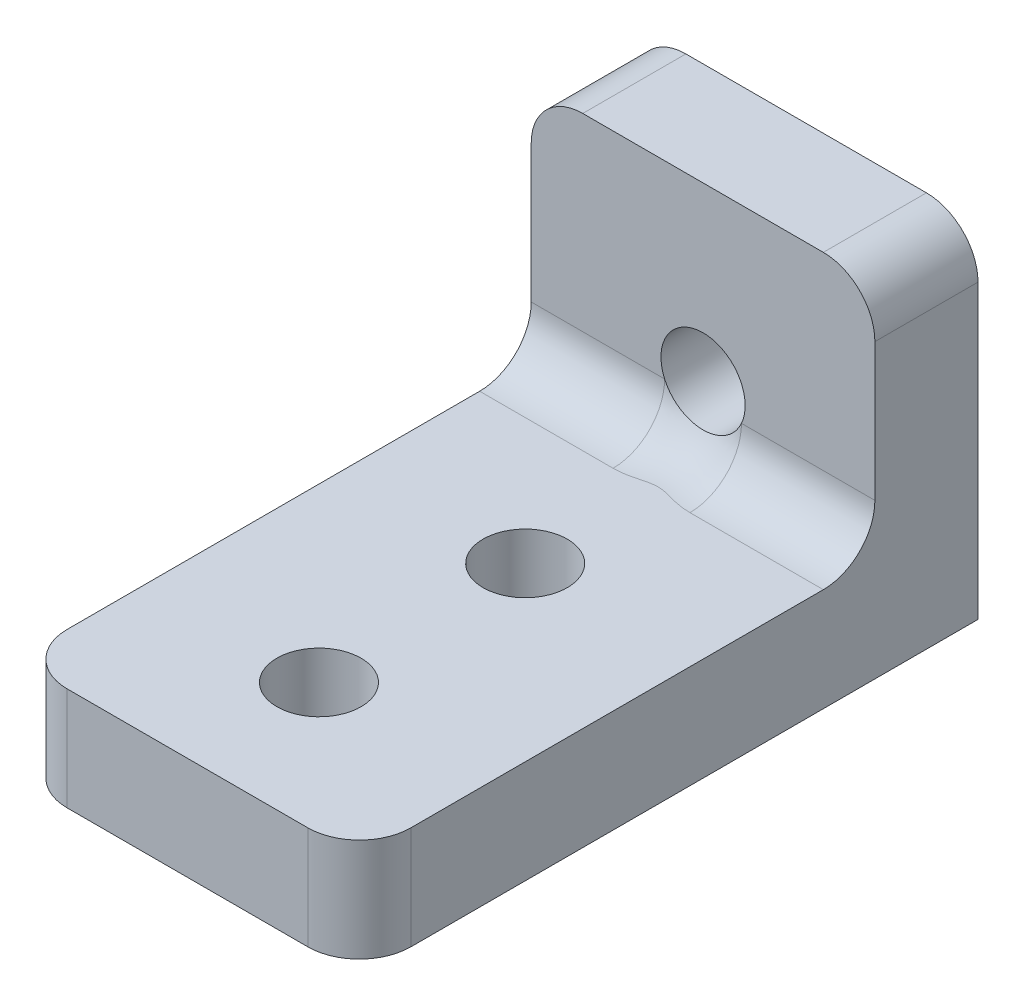
SolidWorks part; units mm, degrees
ref_plane "Front Plane" through (0, 0, 0) normal (0, 0, 1) x (1, 0, 0)
ref_plane "Top Plane" through (0, 0, 0) normal (0, 1, 0) x (1, 0, 0)
ref_plane "Right Plane" through (0, 0, 0) normal (1, 0, 0) x (0, 0, -1)
sketch "Sketch1" plane through (0, 0, 0) normal (0, 0, 1) x (1, 0, 0)
  line L1 (0, 0) -> (20, 0)
  line L2 (0, 0) -> (0, -20)
  line L3 (0, -20) -> (20, -20)
  line L4 (20, 0) -> (20, -20)
  dimension "D1" = 20
  dimension "D2" = 20
extrude "Boss-Extrude1" add sketch "Sketch1" along normal blind 6
sketch "Sketch2" plane through (0, 0, 6) normal (0, 0, 1) x (1, 0, 0)
  line L0 (20, -20) -> (20, 0) construction
  line L1 (0, -20) -> (20, -20)
  line L2 (0, -20) -> (0, -14)
  line L3 (0, -14) -> (20, -14)
  line L4 (20, -20) -> (20, -14)
  dimension "D1" = 6
extrude "Boss-Extrude2" add sketch "Sketch2" along normal blind 30
sketch "Sketch3" plane through (0, 0, 6) normal (0, 0, 1) x (1, 0, 0)
  line L0 (20, 0) -> (0, 0) construction
  circle A0 centre (10, -10) radius 2.45
  dimension "D1" = 4.9
  dimension "D2" = 10
extrude "Cut-Extrude1" cut sketch "Sketch3" against normal through all
sketch "Sketch4" plane through (0, -14, 0) normal (0, 1, 0) x (1, 0, 0)
  line L0 (20, -36) -> (0, -36) construction
  circle A0 centre (10, -28.35) radius 2.45
  dimension "D1" = 4.9
  dimension "D2" = 7.65
extrude "Cut-Extrude2" cut sketch "Sketch4" against normal through all
fillet "Fillet1" radius 3 4 edges at (0, 0, 3) (20, 0, 3) (20, -17, 36) (0, -17, 36)
fillet "Fillet2" radius 3 1 edges at (10, -14, 6)
sketch "Sketch5" plane through (0, -14, 0) normal (0, 1, 0) x (1, 0, 0)
  circle A0 centre (10, -16.35) radius 2.45
  circle A1 centre (10, -28.35) radius 2.45 construction
  dimension "D1" = 4.9
  dimension "D2" = 12
extrude "Cut-Extrude3" cut sketch "Sketch5" against normal through all
equation "\"滑动-垂直孔\"= 0.6"
equation "\"滑动-水平孔\"= 0.3"
equation "\"松动-垂直孔\"= 0.3"
equation "\"松动-水平孔\"= 0.1"
equation "\"正常-垂直孔\"= 0.15"
equation "\"正常-水平孔\"= 0"
equation "\"紧缩-垂直孔\"= 0"
equation "\"紧缩-水平孔\"= - 0.1"
equation "\"D1@Sketch3\"=\"紧缩-水平孔\"+5"
equation "\"D1@Sketch4\"=\"D1@Sketch3\""
equation "\"D1@Sketch5\"=\"D1@Sketch4\""
